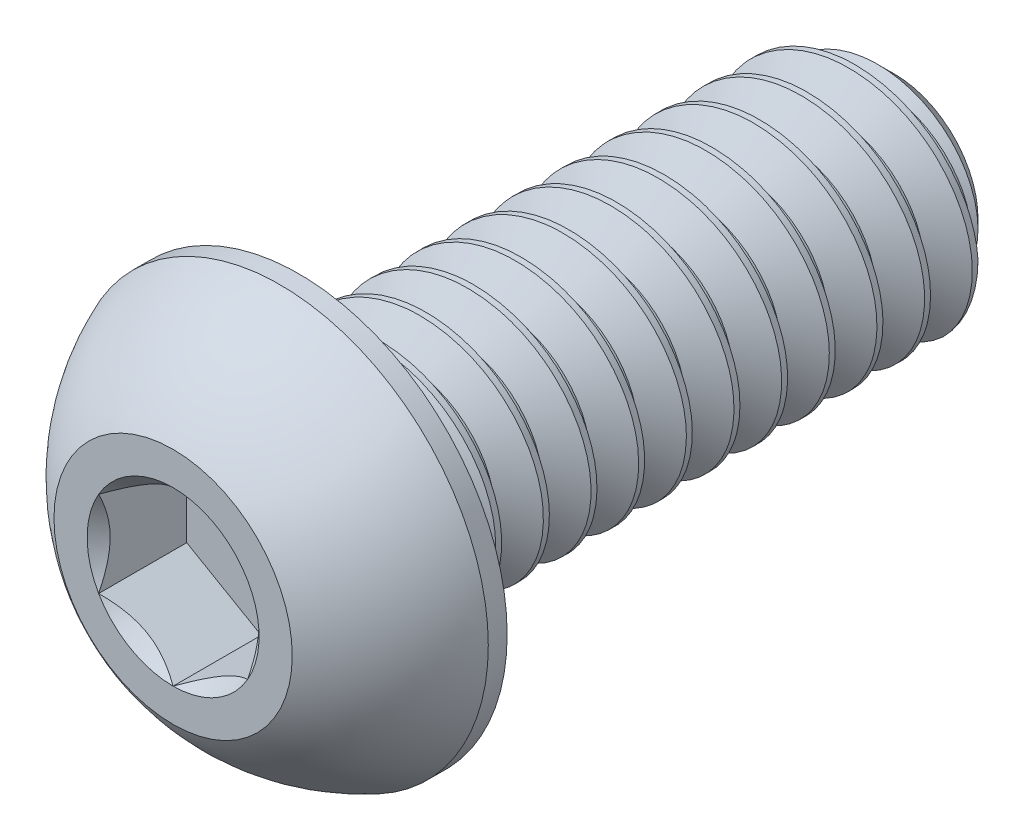
SolidWorks part; units mm, degrees
ref_plane "Front" through (0, 0, 0) normal (0, 0, 1) x (1, 0, 0)
ref_plane "Top" through (0, 0, 0) normal (0, 1, 0) x (1, 0, 0)
ref_plane "Right" through (0, 0, 0) normal (1, 0, 0) x (0, 0, -1)
sketch "Sketch1" plane through (0, 0, 0) normal (1, 0, 0) x (0, 0, -1)
  line L2 (3.3528, 3.175) -> (19.2278, 3.175)
  line L3 (19.2278, 3.175) -> (19.2278, 0)
  line L4 (19.2278, 0) -> (3.3528, 0)
  line L6 (2.8499, 5.5499) -> (3.3528, 5.5499) construction
  line L7 (19.2278, 3.175) -> (19.2278, -3.175) construction
  line L8 (0, 0) -> (3.3528, 0) construction
  line L9 (3.3528, 5.5499) -> (3.3528, -5.5499) construction
  line L11 (3.3528, 3.175) -> (3.3528, 0)
  line L13 (0, 1.9844) -> (0, -1.9844) construction
  line L14 (0, 1.9844) -> (0, 3.175) construction
  arc A3 (0, 3.175) -> (2.8499, 5.5499) centre (5.0603, 0) cw construction
  dimension "D1" = 0.5029
revolve "Revolve1" add sketch "Sketch1" angle 360 mid plane about L4
sketch "Sketch3" plane through (0, 0, -19.2278) normal (0, 0, -1) x (-1, 0, 0)
  circle A0 centre (0, 0) radius 3.175
curve "Helix/Spiral1" pitch 1.27 height 17.145 radius 3.175 centre (0, 0, -19.2278) axis (0, 0, 1) start towards (0, 1, 0)
sketch "Sketch2" plane through (0, 0, 0) normal (1, 0, 0) x (0, 0, -1)
  line L0 (19.2278, 3.175) -> (20.339, 3.175)
  line L1 (20.339, 3.175) -> (19.8628, 2.3501)
  line L2 (19.8628, 2.3501) -> (19.704, 2.3501)
  line L3 (19.704, 2.3501) -> (19.2278, 3.175)
  line L4 (19.4659, 2.7626) -> (20.1009, 2.7626) construction
  dimension "D1" = 60
  dimension "D2" = 0.1588
  dimension "D3" = 0.635
chamfer "Chamfer1" distance 0.9525 angle 45 1 edges at (0, 3.175, -19.2278)
sweep "Cut-Sweep1" cut profiles "Sketch2" path "Helix/Spiral1" align with end faces yes
sketch "Sketch7" plane through (0, 0, 0) normal (1, 0, 0) x (0, 0, -1)
  line L6 (2.8499, 5.5499) -> (3.3528, 5.5499) construction
  line L8 (0, 0) -> (3.3528, 0) construction
  line L11 (3.3528, 5.5499) -> (3.3528, -5.5499) construction
  line L12 (2.8499, 5.5499) -> (3.3528, 5.5499)
  line L13 (0, 0) -> (3.3528, 0)
  line L14 (0, 1.9844) -> (0, -1.9844) construction
  line L15 (3.3528, 5.5499) -> (3.3528, 0)
  line L16 (0, 3.175) -> (0, 0)
  arc A2 (2.8499, 5.5499) -> (0, 3.175) centre (5.0603, 0) ccw construction
  arc A3 (2.8499, 5.5499) -> (0, 3.175) centre (5.0603, 0) ccw
revolve "Revolve2" add sketch "Sketch7" angle 360 mid plane about L13
sketch "Sketch5" plane through (0, 0, 0) normal (0, 0, 1) x (1, 0, 0)
  line L1 (1.9844, -1.1457) -> (1.9844, 1.1457)
  line L2 (1.9844, 1.1457) -> (0, 2.2914)
  line L3 (0, 2.2914) -> (-1.9844, 1.1457)
  line L4 (-1.9844, 1.1457) -> (-1.9844, -1.1457)
  line L5 (-1.9844, -1.1457) -> (0, -2.2914)
  line L6 (0, -2.2914) -> (1.9844, -1.1457)
  circle A0 centre (0, 0) radius 1.9844 construction
extrude "Cut-Extrude2" cut sketch "Sketch5" against normal blind 2.347
sketch "Sketch6" plane through (0, 0, 0) normal (0, 0, 1) x (1, 0, 0)
  circle A0 centre (0, 0) radius 2.2914
extrude "Cut-Extrude3" cut sketch "Sketch6" against normal blind 2.347 draft 45
sketch "Sketch9" [suppressed] plane through (0, 0, -3.3528) normal (0, 0, 1) x (1, 0, 0)
  circle A2 centre (0, 0) radius 3.175
extrude "Boss-Extrude2" [suppressed] add sketch "Sketch9" against normal offset from surface (12.7 mm away) 22.225 up to face at (0, 2.2225, -19.2278)
sketch "Sketch10" plane through (0, 0, 0) normal (1, 0, 0) x (0, 0, -1)
  line L0 (19.2278, 3.175) -> (19.2278, -3.175) construction
  point P0 (17.3228, -3.175)
  dimension "D1" = 1.905
equation "\"D3@Helix/Spiral1\" = \"Lg@Sketch1\" + \"D4@Helix/Spiral1\""
equation "\"D2@Sketch2\" = \"D4@Helix/Spiral1\" * .125"
equation "\"D3@Sketch2\" = \"D4@Helix/Spiral1\" * .5"
equation "\"D1@Chamfer1\" = \"D4@Helix/Spiral1\" * .75"
equation "\"D1@Cut-Extrude2\" = \"Head Ht@Sketch1\" * .7"
equation "\"D1@Sketch1\" = \"Head Ht@Sketch1\" * .15"
equation "\"D1@Sketch10\" = \"D4@Helix/Spiral1\" * 1.5"
equation "\"D1@Cut-Extrude3\" = \"D1@Cut-Extrude2\""
